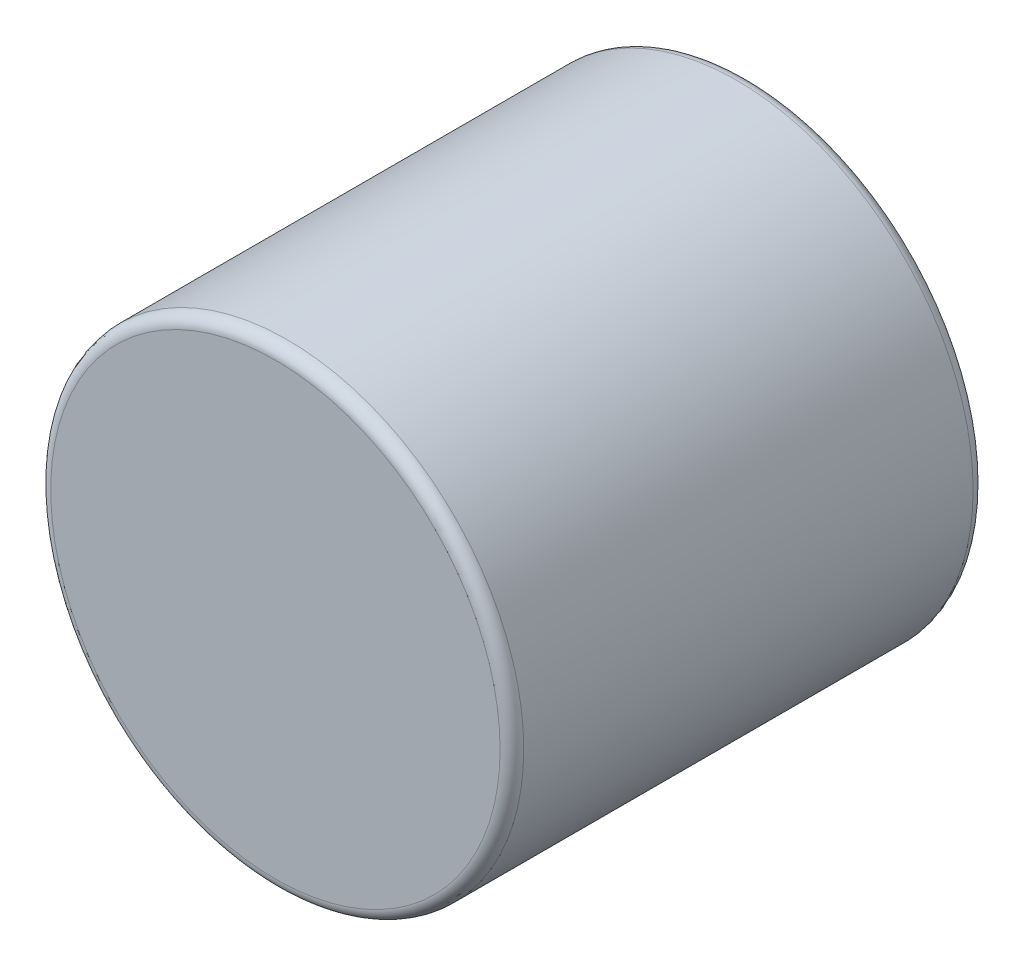
SolidWorks part; units mm, degrees
ref_plane "Front Plane" through (0, 0, 0) normal (0, 0, 1) x (1, 0, 0)
ref_plane "Top Plane" through (0, 0, 0) normal (0, 1, 0) x (1, 0, 0)
ref_plane "Right Plane" through (0, 0, 0) normal (1, 0, 0) x (0, 0, -1)
sketch "Sketch1" plane through (0, 0, 0) normal (0, 0, 1) x (1, 0, 0)
  circle A0 centre (0, 0) radius 1.5875 construction
  dimension "OD" = 3.175
sketch "Sketch2" plane through (0, 0, 0) normal (1, 0, 0) x (0, 0, -1)
  line L0 (-1.5875, 0) -> (1.5875, 0) construction
  line L1 (0, 1.5875) -> (0, -1.5875) construction
  line L3 (-1.5875, 1.5875) -> (1.5875, 1.5875)
  line L4 (-1.5875, 1.5875) -> (-1.5875, -1.5875)
  line L5 (-1.5875, -1.5875) -> (1.5875, -1.5875)
  line L6 (1.5875, 1.5875) -> (1.5875, -1.5875)
  point P4 (0, 0)
  point P12 (0, 1.5875)
  dimension "Thickness" = 3.175
sketch "Sketch3" plane through (0, 0, 0) normal (0, 0, 1) x (1, 0, 0)
  circle A0 centre (0, 0) radius 1.5875 construction
  circle A1 centre (0, 0) radius 1.5875
extrude "Boss-Extrude1" add sketch "Sketch3" along normal up to vertex (1.5875 mm away) and the other way up to vertex (1.5875 mm away) up to point (0, 1.5875, 1.5875) other way up to point (0, 1.5875, -1.5875)
fillet "Fillet1" radius 0.0794 2 edges at (1.5875, 0, -1.5875) (1.5875, 0, 1.5875)
equation "\"Fillet@Fillet1\"=\"Thickness@Sketch2\"*.025"
